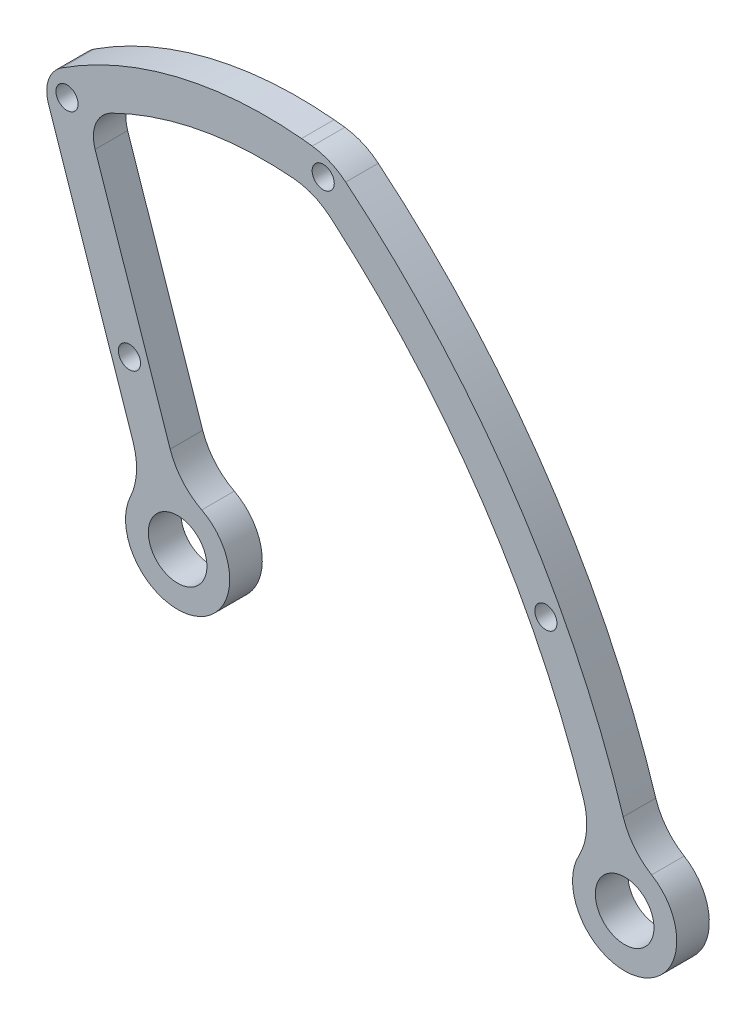
SolidWorks part; units mm, degrees
material "A2017"
ref_plane "正面" through (0, 0, 0) normal (0, 0, 1) x (1, 0, 0)
ref_plane "平面" through (0, 0, 0) normal (0, 1, 0) x (1, 0, 0)
ref_plane "右側面" through (0, 0, 0) normal (1, 0, 0) x (0, 0, -1)
sketch "ｽｹｯﾁ2" plane through (0, 0, 0) normal (0, 0, 1) x (1, 0, 0)
  line L4 (-103.4721, 101.9749) -> (-90.4656, 63.494)
  line L5 (-84.7815, 65.4152) -> (-96.3061, 99.5117)
  circle A0 centre (-91.0319, 74.5383) radius 1
  circle A1 centre (-100.6248, 104.2316) radius 1
  circle A2 centre (-61.2846, 113.3479) radius 1
  circle A3 centre (-27.0948, 71.9322) radius 1
  circle A21 centre (-100.6248, 104.2316) radius 1.5 construction
  circle A22 centre (-61.2846, 113.3479) radius 1.5 construction
  circle A23 centre (-91.0319, 74.5383) radius 1.5 construction
  circle A24 centre (-83.6371, 52.6602) radius 4.5
  circle A25 centre (-27.0948, 71.9322) radius 1.5 construction
  circle A26 centre (-15, 38.9143) radius 4.5
  arc A30 (-15.2219, 51.2935) -> (-57.8253, 114.4005) centre (-143.6936, 10.4967) ccw
  arc A31 (-57.8253, 114.4005) -> (-62.9665, 116.6163) centre (-64.1956, 106.6922) ccw
  arc A32 (-62.9665, 116.6163) -> (-64.6165, 116.798) centre (-70.4705, 56.0286) ccw
  arc A33 (-64.6165, 116.798) -> (-101.462, 107.7671) centre (-70.1265, 59.5994) ccw
  arc A34 (-101.462, 107.7671) -> (-103.4721, 101.9749) centre (-98.7354, 103.5759) ccw
  arc A35 (-90.8824, 56.0521) -> (-90.4656, 63.494) centre (-99.9391, 60.2919) ccw
  arc A36 (-90.8824, 56.0521) -> (-79.9353, 59.7522) centre (-83.6371, 52.6602) ccw
  arc A37 (-84.7815, 65.4152) -> (-79.9353, 59.7522) centre (-75.308, 68.6172) ccw
  arc A38 (-93.7791, 105.5979) -> (-96.3061, 99.5117) centre (-91.5694, 101.1127) ccw
  arc A39 (-65.8029, 110.8809) -> (-93.7791, 105.5979) centre (-70.2884, 57.9186) ccw
  arc A40 (-60.161, 108.5281) -> (-65.8029, 110.8809) centre (-66.6468, 100.9166) ccw
  arc A41 (-21.3117, 50.6279) -> (-60.161, 108.5281) centre (-143.6936, 10.4967) ccw
  arc A42 (-22.0284, 42.7355) -> (-21.3117, 50.6279) centre (-30.8139, 47.512) ccw
  arc A43 (-22.0284, 42.7355) -> (-10.8626, 45.7613) centre (-15, 38.9143) ccw
  arc A44 (-15.2219, 51.2935) -> (-10.8626, 45.7613) centre (-5.6909, 54.3201) ccw
  dimension "D1" = 9
  dimension "D2" = 2
extrude "ﾎﾞｽ - 押し出し1" add sketch "ｽｹｯﾁ2" along normal blind 5
hole_wizard "M3 すきま穴1" positions "ｽｹｯﾁ3" profile "ｽｹｯﾁ4" hole size "M3" standard "JIS" end condition through all
sketch "ｽｹｯﾁ3" plane through (0, 0, 5) normal (0, 0, 1) x (1, 0, 0)
  point P0 (-91.0319, 74.5383)
  point P3 (-100.6248, 104.2316)
  point P6 (-61.2846, 113.3479)
  point P9 (-27.0948, 71.9322)
sketch "ｽｹｯﾁ4" plane through (-91.0319, 74.5383, 5) normal (1, 0, 0) x (0, -1, 0)
  line L0 (0, 0) -> (0, 5)
  line L1 (0, 5) -> (1.7, 5)
  line L2 (1.7, 5) -> (1.7, 0)
  line L5 (1.7, 0) -> (0, 0)
  line L11 (0, -6.35) -> (0, 107.95) construction
  dimension "通し穴の直径" = 3.4
  dimension "通し穴の深さ" = 5
